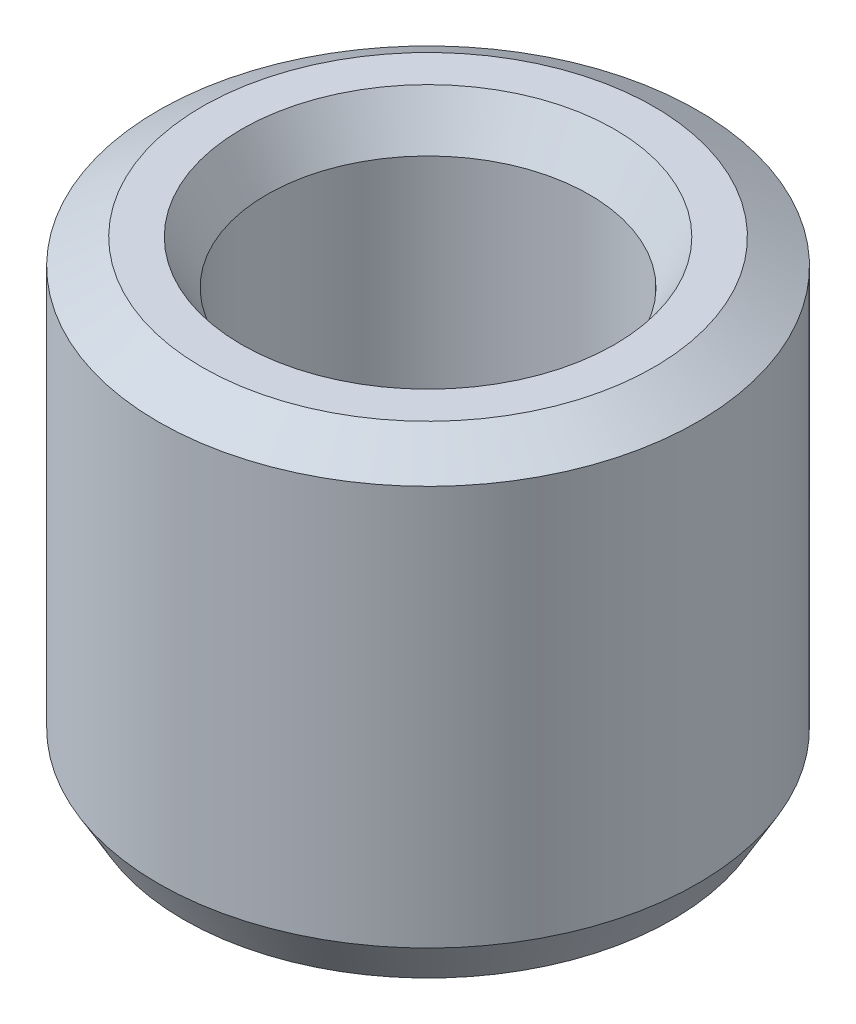
SolidWorks part; units mm, degrees
ref_plane "Front Plane" through (0, 0, 0) normal (0, 0, 1) x (1, 0, 0)
ref_plane "Top Plane" through (0, 0, 0) normal (0, 1, 0) x (1, 0, 0)
ref_plane "Right Plane" through (0, 0, 0) normal (1, 0, 0) x (0, 0, -1)
sketch "Sketch1" plane through (0, 0, 0) normal (0, 1, 0) x (1, 0, 0)
  circle A0 centre (0, 0) radius 30
  dimension "SLEEVE_OD" = 60
extrude "Boss-Extrude1" add sketch "Sketch1" along normal blind 52.1715
sketch "Sketch2" plane through (0, 0, 0) normal (0, 1, 0) x (1, 0, 0)
  circle A0 centre (0, 0) radius 17.9282
  dimension "BORE_D" = 35.8563
extrude "Cut-Extrude1" cut sketch "Sketch2" along normal through all
chamfer "Chamfer1" distance 2.8178 angle 60 4 edges at (0, 52.1715, 17.9282) (0, 0, 17.9282) (0, 0, 30) (0, 52.1715, 30) first distance on face at (0, 52.1715, 17.9282) first distance on face at (0, 0, 17.9282) first distance on face at (0, 52.1715, 30)
